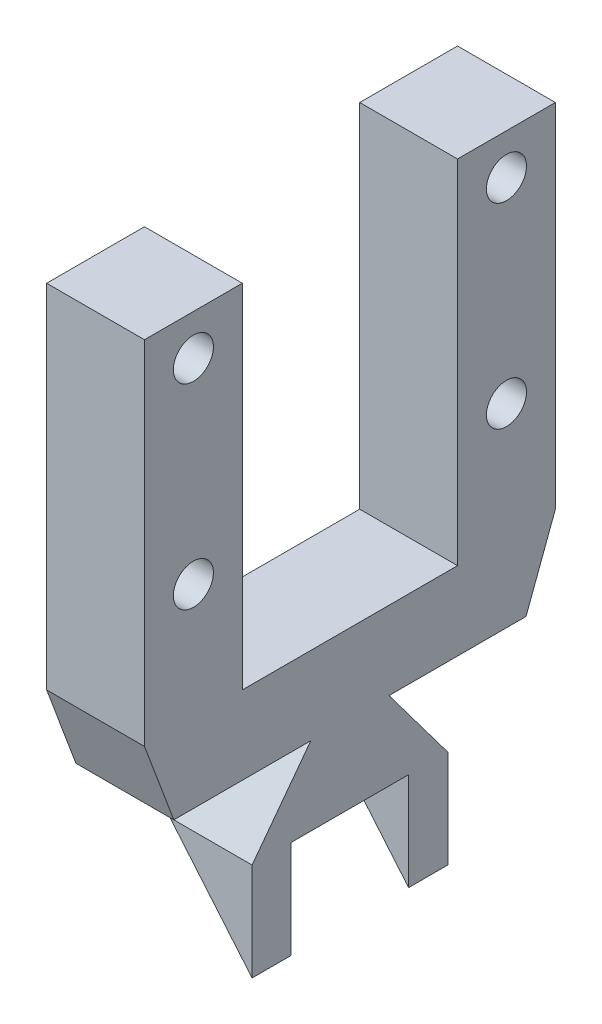
SolidWorks part; units mm, degrees
material "ABS"
ref_plane "Front Plane" through (0, 0, 0) normal (0, 0, 1) x (1, 0, 0)
ref_plane "Top Plane" through (0, 0, 0) normal (0, 1, 0) x (1, 0, 0)
ref_plane "Right Plane" through (0, 0, 0) normal (1, 0, 0) x (0, 0, -1)
sketch "Sketch5" plane through (0, 0, 0) normal (1, 0, 0) x (0, 0, -1)
  line L0 (-6.35, 0) -> (6.35, 0)
  line L1 (-11.43, 5.08) -> (-2.54, 5.08)
  line L3 (-13.335, 33.02) -> (-6.985, 33.02)
  line L5 (55, 0) -> (-55, 0) construction
  line L6 (6.35, 0) -> (2.54, 5.08)
  line L7 (-6.35, 0) -> (-2.54, 5.08)
  line L8 (2.54, 5.08) -> (11.43, 5.08)
  line L9 (6.985, 33.02) -> (13.335, 33.02)
  line L10 (-6.985, 10.16) -> (6.985, 10.16)
  line L11 (-6.985, 10.16) -> (-6.985, 33.02)
  line L13 (6.985, 10.16) -> (6.985, 33.02)
  line L14 (-11.43, 5.08) -> (-13.335, 10.16)
  line L15 (-13.335, 10.16) -> (-13.335, 33.02)
  line L16 (11.43, 5.08) -> (13.335, 10.16)
  line L17 (13.335, 10.16) -> (13.335, 33.02)
  point P1 (0, 0)
  point P2 (2.2566, 5.08)
  point P9 (0, 0)
  point P13 (0, 0)
  point P14 (0, 10.16)
  point P22 (-12.7, 6.0325)
  point P23 (-12.7, 10.16)
  point P24 (0, 0)
  dimension "D1" = 22.86
  dimension "D2" = 26.67
  dimension "D3" = 5.08
  dimension "D4" = 12.7
  dimension "D5" = 5.08
  dimension "D6" = 5.08
  dimension "D7" = 6.35
  dimension "D8" = 27.94
extrude "Boss-Extrude2" add sketch "Sketch5" along normal blind 6.35
sketch "Sketch7" plane through (0, 0, 0) normal (0, 0, 1) x (1, 0, 0)
  line L0 (6.35, 0) -> (6.35, -6.35)
  line L1 (6.35, -6.35) -> (1.0217, 0)
  line L2 (6.35, 0) -> (0, 0) construction
  line L3 (1.0217, 0) -> (6.35, 0)
  dimension "D1" = 6.35
  dimension "D2" = 40
extrude "Boss-Extrude4" add sketch "Sketch7" along normal mid plane 12.7
extrude "Cut-Extrude1" cut sketch "Sketch7<2>" against normal mid plane 7.62
sketch "Sketch7<2>" plane through (0, 0, 0) normal (0, 0, 1) x (1, 0, 0) same geometry as "Sketch7"
hole_wizard "M2 Clearance Hole1" positions "Sketch10" profile "Sketch12" hole size "M2" standard "ANSI Metric" end condition through all
sketch "Sketch10" plane through (6.35, 0, 0) normal (1, 0, 0) x (0, 0, -1)
  point P2 (-10.16, 17.6898)
  point P5 (-10.16, 30.3898)
  point P8 (10.16, 30.3898)
  point P11 (10.16, 17.6898)
sketch "Sketch12" plane through (6.35, 17.6898, 10.16) normal (0, 1, 0) x (0, 0, -1)
  line L0 (0, 0) -> (0, 6.35)
  line L1 (0, 6.35) -> (1.3, 6.35)
  line L2 (1.3, 6.35) -> (1.3, 0)
  line L5 (1.3, 0) -> (0, 0)
  line L11 (0, -6.35) -> (0, 107.95) construction
  dimension "Thru Hole Dia." = 2.6
  dimension "Thru Hole Depth" = 6.35
